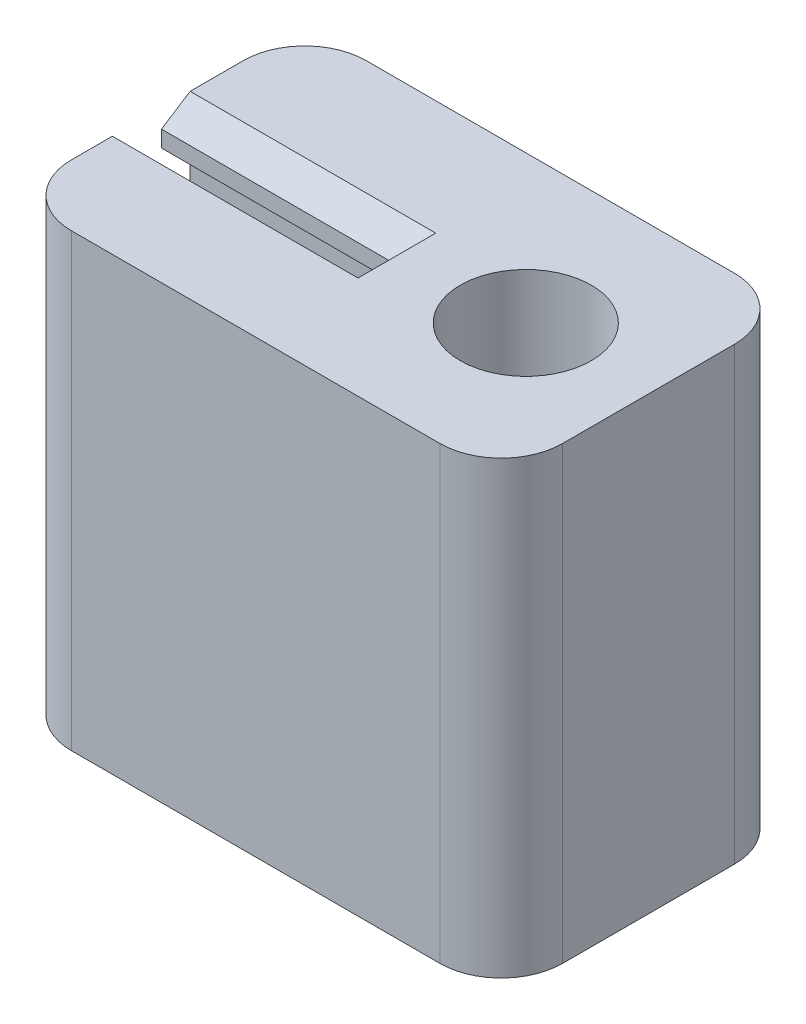
SolidWorks part; units mm, degrees
material "ABS"
ref_plane "Front Plane" through (0, 0, 0) normal (0, 0, 1) x (1, 0, 0)
ref_plane "Top Plane" through (0, 0, 0) normal (0, 1, 0) x (1, 0, 0)
ref_plane "Right Plane" through (0, 0, 0) normal (1, 0, 0) x (0, 0, -1)
sketch "Sketch1" plane through (0, 0, 0) normal (0, 1, 0) x (1, 0, 0)
  line L0 (-6, 0) -> (6, 0) construction
  line L1 (-4.5, -3.6) -> (4.5, -3.6)
  line L2 (-6, -2.1) -> (-6, 2.1)
  line L3 (-4.5, 3.6) -> (4.5, 3.6)
  line L4 (6, -2.1) -> (6, 2.1)
  line L5 (-6, -3.6) -> (6, 3.6) construction
  line L6 (-6, 3.6) -> (6, -3.6) construction
  circle A0 centre (3, 0) radius 1.6
  arc A1 (4.5, 3.6) -> (6, 2.1) centre (4.5, 2.1) cw
  arc A2 (6, -2.1) -> (4.5, -3.6) centre (4.5, -2.1) cw
  arc A3 (-4.5, -3.6) -> (-6, -2.1) centre (-4.5, -2.1) cw
  arc A4 (-6, 2.1) -> (-4.5, 3.6) centre (-4.5, 2.1) cw
  point P0 (0, 0)
  dimension "D3" = 3.2
  dimension "D4" = 3
  dimension "D5" = 1.5
  dimension "D1" = 7.2
  dimension "D2" = 12
extrude "Boss-Extrude1" add sketch "Sketch1" against normal blind 11
sketch "Sketch2" plane through (-6, 0, 0) normal (-1, 0, 0) x (0, 0, 1)
  line L0 (-3.6, -11) -> (-3.6, 0) construction
  line L1 (-2.1, 0) -> (2.1, 0) construction
  line L2 (-2.1, -11) -> (2.1, -11) construction
  line L3 (0, 0) -> (0, -11) construction
  line L4 (1.1, -11) -> (-0.3334, -11)
  line L5 (1.1, 0) -> (1.1, -11)
  line L6 (1.1, 0) -> (-0.8, 0)
  line L7 (-0.8, 0) -> (-0.1, -0.45)
  line L8 (-0.1, -0.45) -> (-0.1, -0.85)
  line L9 (-0.1, -0.85) -> (-0.8, -1.3)
  line L10 (-0.8, -1.3) -> (-0.8, -1.65)
  line L11 (-0.1, -0.65) -> (-0.8, -0.65) construction
  line L12 (-0.8, 0) -> (-0.8, 0.35)
  line L13 (-0.8, 0) -> (-0.8, -1.3) construction
  line L14 (-0.8, -2) -> (-0.8, -1.65)
  line L15 (-0.8, -2) -> (-0.1, -2.45)
  line L16 (-0.1, -2.45) -> (-0.1, -2.85)
  line L17 (-0.1, -2.85) -> (-0.8, -3.3)
  line L18 (-0.8, -3.3) -> (-0.8, -3.65)
  line L19 (-0.8, -4) -> (-0.8, -3.65)
  line L20 (-0.8, -4) -> (-0.1, -4.45)
  line L21 (-0.1, -4.45) -> (-0.1, -4.85)
  line L22 (-0.1, -4.85) -> (-0.8, -5.3)
  line L23 (-0.8, -5.3) -> (-0.8, -5.65)
  line L24 (-0.8, -6) -> (-0.8, -5.65)
  line L25 (-0.8, -6) -> (-0.1, -6.45)
  line L26 (-0.1, -6.45) -> (-0.1, -6.85)
  line L27 (-0.1, -6.85) -> (-0.8, -7.3)
  line L28 (-0.8, -7.3) -> (-0.8, -7.65)
  line L29 (-0.8, -8) -> (-0.8, -7.65)
  line L30 (-0.8, -8) -> (-0.1, -8.45)
  line L31 (-0.1, -8.45) -> (-0.1, -8.85)
  line L32 (-0.1, -8.85) -> (-0.8, -9.3)
  line L33 (-0.8, -9.3) -> (-0.8, -9.65)
  line L34 (-0.8, -10) -> (-0.8, -9.65)
  line L35 (-0.8, -10) -> (-0.1, -10.45)
  line L36 (-0.1, -10.45) -> (-0.1, -10.85)
  line L37 (-0.1, -10.85) -> (-0.3334, -11)
  line L40 (-0.8, -11.3) -> (-0.8, -11.65) [skipped]
  point P9 (-0.8, -0.65)
  line M1 (2.1, 0) -> (-2.1, 0)
  line M3 (-2.1, -11) -> (2.1, -11)
  dimension "D1" = 1.2
  dimension "D2" = 0.7
  dimension "D3" = 6
  dimension "D4" = 0.35
  dimension "D5" = 0.4
  dimension "D6" = 3.5
  dimension "D7" = 2
  dimension "D9" = 0.35
  dimension "D10" = 2
extrude "Cut-Extrude1" cut sketch "Sketch2" against normal blind 6 contours L36 L37 L5 L7 L8 L9 L10 L14 L15 L16 L17 L18 L19 L20 L21 L22 L23 L24 L25 L26 L27 L28 L29 L30 L31 L32 L33 L34 L35 M3 M1 region at (-6, -5.4918, 0.2826)
sketch "Sketch3" [suppressed] plane through (0, -11, 0) normal (0, -1, 0) x (1, 0, 0)
  line L12 (0, 1.1) -> (-6, 1.1) construction
  line L13 (0, -0.3334) -> (0, 1.1) construction
  line L14 (0, -0.3334) -> (-6, -0.3334) construction
  line L15 (-4.5, -6.6) -> (4.5, -6.6)
  line L16 (9, -2.1) -> (9, 2.1)
  line L17 (4.5, 6.6) -> (-4.5, 6.6)
  line L18 (-4.5, -6.6) -> (4.5, -6.6)
  line L19 (9, -2.1) -> (9, 2.1)
  line L20 (4.5, 6.6) -> (-4.5, 6.6)
  line L21 (0, 1.1) -> (-9, 1.1)
  line L22 (0, -0.3334) -> (0, 1.1)
  line L23 (0, -0.3334) -> (-9, -0.3334)
  line L24 (-9, 2.1) -> (-9, 1.1)
  line L25 (-9, -0.3334) -> (-9, -2.1)
  arc A20 (-9, -2.1) -> (-4.5, -6.6) centre (-4.5, -2.1) ccw
  arc A21 (4.5, -6.6) -> (9, -2.1) centre (4.5, -2.1) ccw
  arc A22 (9, 2.1) -> (4.5, 6.6) centre (4.5, 2.1) ccw
  arc A23 (-4.5, 6.6) -> (-9, 2.1) centre (-4.5, 2.1) ccw
  arc A24 (-9, -2.1) -> (-4.5, -6.6) centre (-4.5, -2.1) ccw
  arc A25 (4.5, -6.6) -> (9, -2.1) centre (4.5, -2.1) ccw
  arc A26 (9, 2.1) -> (4.5, 6.6) centre (4.5, 2.1) ccw
  arc A27 (-4.5, 6.6) -> (-9, 2.1) centre (-4.5, 2.1) ccw
  dimension "D1" = 3
extrude "Boss-Extrude2" [suppressed] add sketch "Sketch3" against normal blind 0.44
